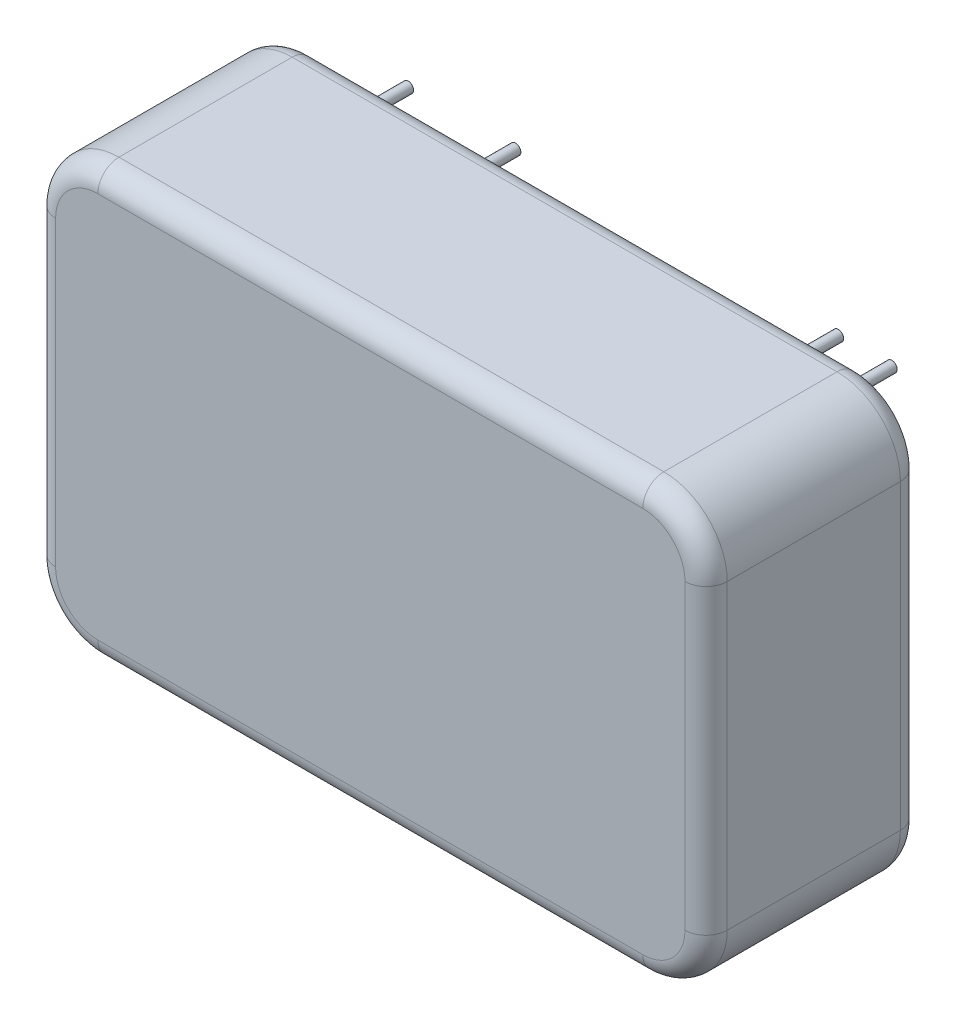
SolidWorks part; units mm, degrees
ref_plane "Спереди" through (0, 0, 0) normal (0, 0, 1) x (1, 0, 0)
ref_plane "Сверху" through (0, 0, 0) normal (0, 1, 0) x (1, 0, 0)
ref_plane "Справа" through (0, 0, 0) normal (1, 0, 0) x (0, 0, -1)
sketch "Эскиз1" plane through (0, 0, 0) normal (0, 0, 1) x (1, 0, 0)
  line L1 (-15.9, -10.15) -> (15.9, -10.15)
  line L2 (-15.9, -10.15) -> (-15.9, 10.15)
  line L3 (-15.9, 10.15) -> (15.9, 10.15)
  line L4 (15.9, -10.15) -> (15.9, 10.15)
  line L5 (-15.9, -10.15) -> (15.9, 10.15) construction
  line L6 (-15.9, 10.15) -> (15.9, -10.15) construction
  point P0 (0, 0)
  dimension "D1" = 31.8
  dimension "D2" = 20.3
extrude "Бобышка-Вытянуть1" add sketch "Эскиз1" along normal blind 10.2
fillet "Скругление2" radius 1 8 edges at (0, 10.15, 0) (15.9, 0, 0) (0, -10.15, 0) (-15.9, 0, 0) (0, 10.15, 10.2) (15.9, 0, 10.2) (0, -10.15, 10.2) (-15.9, 0, 10.2)
fillet "Скругление1" radius 3 12 edges at (-15.9, -10.15, 5.1) (15.9, -10.15, 5.1) (15.9, 10.15, 5.1) (-15.9, 10.15, 5.1) (-15.6071, 9.8571, 0.2929) (-15.6071, 9.8571, 9.9071) (15.6071, 9.8571, 0.2929) (15.6071, 9.8571, 9.9071) (15.6071, -9.8571, 0.2929) (15.6071, -9.8571, 9.9071) (-15.6071, -9.8571, 0.2929) (-15.6071, -9.8571, 9.9071)
sketch "Эскиз2" plane through (0, 0, 0) normal (0, 0, -1) x (-1, 0, 0)
  circle A0 centre (11.45, 7.62) radius 0.25
  circle A1 centre (6.37, 7.62) radius 0.25
  circle A2 centre (-8.91, 7.62) radius 0.25
  circle A3 centre (-11.45, 7.62) radius 0.25
  circle A4 centre (-11.45, -7.62) radius 0.25
  circle A5 centre (-8.91, -7.62) radius 0.25
  circle A6 centre (6.37, -7.62) radius 0.25
  circle A7 centre (11.45, -7.62) radius 0.25
  dimension "D1" = 0.5
  dimension "D2" = 7.62
  dimension "D3" = 7.62
  dimension "D4" = 5.08
  dimension "D5" = 2.54
  dimension "D6" = 22.9
  dimension "D7" = 11.45
extrude "Бобышка-Вытянуть2" add sketch "Эскиз2" along normal blind 3.05
